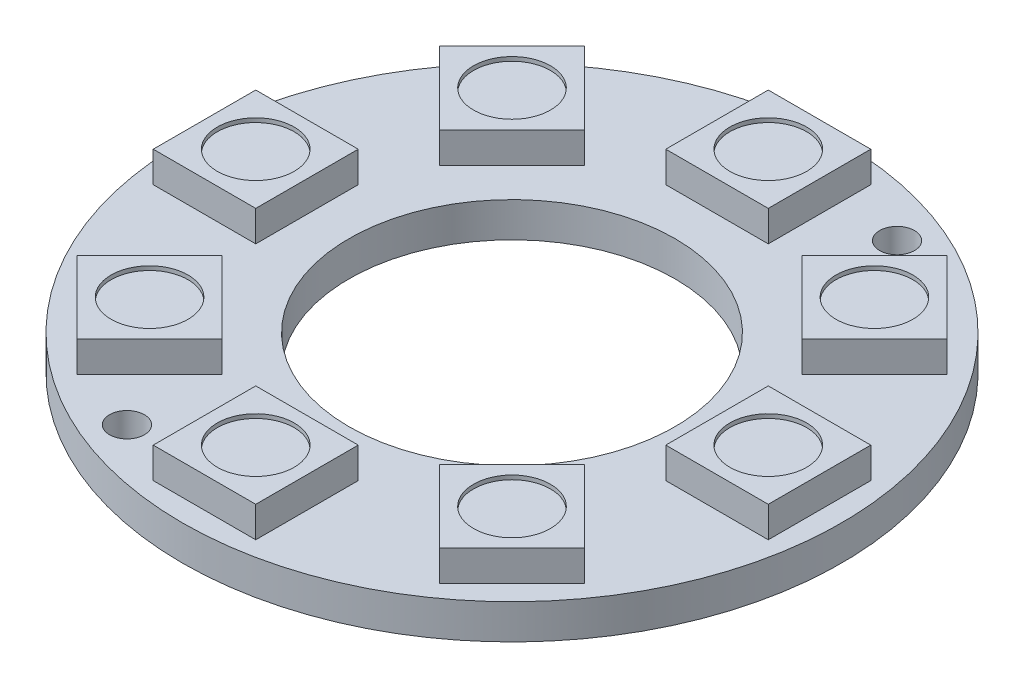
SolidWorks part; units mm, degrees
ref_plane "Plan de face" through (0, 0, 0) normal (0, 0, 1) x (1, 0, 0)
ref_plane "Plan de dessus" through (0, 0, 0) normal (0, 1, 0) x (1, 0, 0)
ref_plane "Plan de droite" through (0, 0, 0) normal (1, 0, 0) x (0, 0, -1)
sketch "Esquisse1" plane through (0, 0, 0) normal (0, 1, 0) x (1, 0, 0)
  line L0 (0, 0) -> (0, 16.075) construction
  line L1 (0, 0) -> (6.1516, 14.8514) construction
  line L2 (-7.3448, 3.0423) -> (0, 0) construction
  circle A0 centre (0, 0) radius 7.95
  circle A1 centre (0, 0) radius 16.075
  circle A2 centre (5.5011, 13.2808) radius 0.85
  circle A3 centre (-5.5011, -13.2808) radius 0.85
  dimension "D1" = 32.15
  dimension "D2" = 15.9
  dimension "D5" = 1.7
  dimension "D3" = 22.5
  dimension "D4" = 14.375
extrude "Boss.-Extru.1" add sketch "Esquisse1" along normal blind 1.7
sketch "Esquisse3" plane through (0, 0, 0) normal (0, -1, 0) x (1, 0, 0)
  line L0 (0, 0) -> (-16.075, 0) construction
  line L1 (-10.45, -5.5) -> (-13.45, -5.5)
  line L2 (-10.45, -5.5) -> (-10.45, -3.5)
  line L3 (-10.45, -3.5) -> (-13.45, -3.5)
  line L4 (-13.45, -5.5) -> (-13.45, -3.5)
  line L5 (-10.45, -5.5) -> (-10.45, 5.5) construction
  line L6 (-10.45, -2.5) -> (-13.45, -2.5)
  line L7 (-10.45, -2.5) -> (-10.45, -0.5)
  line L8 (-10.45, -0.5) -> (-13.45, -0.5)
  line L9 (-13.45, -2.5) -> (-13.45, -0.5)
  line L10 (-13.45, -5.5) -> (-13.45, 5.5) construction
  line L11 (-7.95, 0) -> (-7.95, -13.9715) construction
  line L12 (-13.45, 2.5) -> (-13.45, 0.5)
  line L13 (-10.45, 0.5) -> (-13.45, 0.5)
  line L14 (-10.45, 2.5) -> (-10.45, 0.5)
  line L15 (-10.45, 2.5) -> (-13.45, 2.5)
  line L16 (-13.45, 5.5) -> (-13.45, 3.5)
  line L17 (-10.45, 3.5) -> (-13.45, 3.5)
  line L18 (-10.45, 5.5) -> (-10.45, 3.5)
  line L19 (-10.45, 5.5) -> (-13.45, 5.5)
  circle A0 centre (0, 0) radius 16.075 construction
  circle A1 centre (0, 0) radius 7.95 construction
  point P23 (-13.45, 0)
  point P24 (-10.45, 0)
  dimension "D1" = 3
  dimension "D2" = 2
  dimension "D3" = 2
  dimension "D4" = 1
  dimension "D5" = 0.5
  dimension "D6" = 2.5
extrude "Boss.-Extru.2" add sketch "Esquisse3" along normal blind 0.1
sketch "Esquisse4" plane through (0, 1.7, 0) normal (0, 1, 0) x (1, 0, 0)
  line L0 (0, 0) -> (0, 16.075) construction
  line L2 (-2.5, 15) -> (2.5, 15)
  line L3 (-2.5, 15) -> (-2.5, 10)
  line L4 (-2.5, 10) -> (2.5, 10)
  line L5 (2.5, 15) -> (2.5, 10)
  circle A0 centre (0, 0) radius 16.075 construction
  dimension "D1" = 5
  dimension "D2" = 5
  dimension "D3" = 10
extrude "Boss.-Extru.3" add sketch "Esquisse4" along normal blind 1.5
sketch "Esquisse5" plane through (0, 3.2, 0) normal (0, 1, 0) x (1, 0, 0)
  line L0 (-2.5, 12.5) -> (2.5, 12.5) construction
  line L1 (-2.5, 15) -> (-2.5, 10) construction
  line L2 (2.5, 10) -> (2.5, 15) construction
  circle A0 centre (0, 12.5) radius 1.875
  dimension "D1" = 3.75
extrude "Enlèv. mat.-Extru.1" cut sketch "Esquisse5" against normal blind 0.2
pattern_circular "Répétition circulaire1" count 8 over 360 about axis through (0, 1.7, 0) along (0, -1, 0) of "Boss.-Extru.3", "Enlèv. mat.-Extru.1" reverse direction yes
sketch "Esquisse6" plane through (0, 0, 0) normal (0, -1, 0) x (1, 0, 0)
  line L0 (-15.25, -5.1) -> (-13.45, -5.1) construction
  line L1 (-13.45, -3.5) -> (-13.45, -5.5) construction
  line L3 (-15.25, -5.1) -> (-15.25, 5.0836) construction
  line L4 (-13.45, -3.5) -> (-13.45, -5.5) construction
  line L5 (-13.45, -5.5) -> (-10.45, -5.5) construction
  line L6 (-13.45, -2.1) -> (-15.9372, -2.1) construction
  line L7 (-13.45, -0.5) -> (-13.45, -2.5) construction
  line L8 (-13.45, 0.9) -> (-16.0498, 0.9) construction
  line L9 (-13.45, 2.5) -> (-13.45, 0.5) construction
  line L10 (-13.45, 3.9) -> (-15.25, 3.9) construction
  line L11 (-13.45, 5.5) -> (-13.45, 3.5) construction
  circle A0 centre (0, 0) radius 16.075 construction
  text T0 "DI" font "Century Gothic" height in points 4
  text T1 "5V" font "Century Gothic" height in points 4
  text T2 "GND" font "Century Gothic" height in points 3
  text T3 "D0\r\n" font "Century Gothic" height in points 3
  dimension "D1" = 1.8
  dimension "D2" = 0.4
  dimension "D3" = 3
  dimension "D4" = 3
  dimension "D5" = 3
extrude "Boss.-Extru.4" add sketch "Esquisse6" along normal blind 0.1
